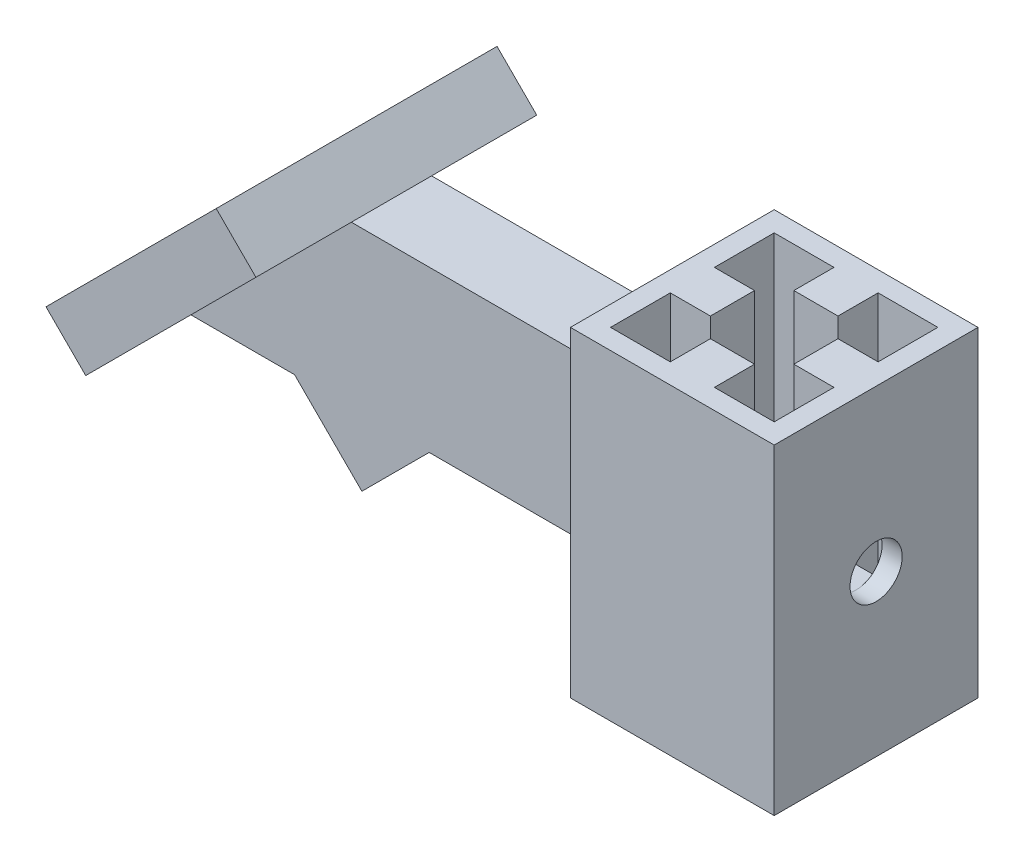
SolidWorks part; units mm, degrees
ref_plane "Alzado" through (0, 0, 0) normal (0, 0, 1) x (1, 0, 0)
ref_plane "Planta" through (0, 0, 0) normal (0, 1, 0) x (1, 0, 0)
ref_plane "Vista lateral" through (0, 0, 0) normal (1, 0, 0) x (0, 0, -1)
sketch "Croquis1" plane through (0, 0, 0) normal (0, 1, 0) x (1, 0, 0)
  line L0 (-12.7, 12.7) -> (12.7, 12.7)
  line L1 (-10.2, 10.2) -> (-2.75, 10.2)
  line L2 (-10.2, 10.2) -> (-10.2, 2.75)
  line L3 (-10.2, -10.2) -> (-2.75, -10.2)
  line L4 (10.2, 10.2) -> (10.2, 2.75)
  line L5 (-10.2, 10.2) -> (10.2, -10.2) construction
  line L6 (-10.2, -10.2) -> (10.2, 10.2) construction
  line L7 (12.7, 12.7) -> (12.7, -12.7)
  line L8 (-12.7, -12.7) -> (12.7, -12.7)
  line L9 (-12.7, 12.7) -> (-12.7, -12.7)
  line L10 (0, 12.7) -> (0, -12.7) construction
  line L11 (-12.7, 0) -> (12.7, 0) construction
  line L12 (-2.75, 10.2) -> (-2.75, 5.2)
  line L13 (-2.75, 5.2) -> (2.75, 5.2)
  line L14 (-10.2, 2.75) -> (-5.2, 2.75)
  line L15 (-5.2, 2.75) -> (-5.2, -2.75)
  line L16 (2.75, 10.2) -> (2.75, 5.2)
  line L17 (-10.2, -2.75) -> (-5.2, -2.75)
  line L18 (2.75, -10.2) -> (2.75, -5.2)
  line L19 (-2.75, -5.2) -> (2.75, -5.2)
  line L20 (-2.75, -10.2) -> (-2.75, -5.2)
  line L21 (10.2, -2.75) -> (5.2, -2.75)
  line L22 (5.2, 2.75) -> (5.2, -2.75)
  line L23 (10.2, 2.75) -> (5.2, 2.75)
  line L24 (2.75, 10.2) -> (10.2, 10.2)
  line L25 (-10.2, 10.2) -> (10.2, 10.2) construction
  line L26 (10.2, -2.75) -> (10.2, -10.2)
  line L27 (10.2, 10.2) -> (10.2, -10.2) construction
  line L28 (2.75, -10.2) -> (10.2, -10.2)
  line L29 (-10.2, -10.2) -> (10.2, -10.2) construction
  line L30 (-10.2, -2.75) -> (-10.2, -10.2)
  line L31 (-10.2, 10.2) -> (-10.2, -10.2) construction
  point P0 (0, 0)
  point P22 (0, 5.2)
  point P23 (-5.2, 0)
  dimension "D1" = 20.4
  dimension "D2" = 20.4
  dimension "D4" = 5
  dimension "D5" = 5.5
  dimension "D3" = 2.5
extrude "Saliente-Extruir1" add sketch "Croquis1" along normal blind 40
sketch "Croquis4" plane through (0, 0, 0) normal (0, 0, 1) x (1, 0, 0)
  line L5 (-12.7, 20) -> (-102.7, 20) construction
  line L11 (-70.7815, 11.8683) -> (-49.5683, 33.0815) construction
  line L14 (-52.0431, 35.5563) -> (-47.0934, 30.6066)
  line L16 (-73.2563, 14.3431) -> (-68.3066, 9.3934)
  line L17 (-73.2563, 14.3431) -> (-52.0431, 35.5563)
  line L18 (-68.3066, 9.3934) -> (-47.0934, 30.6066)
  line L19 (-12.7, 40) -> (-12.7, 0) construction
  line L20 (0, 40) -> (0, 59.061) construction
  line L21 (-12.7, 40) -> (12.7, 40) construction
  line L22 (0, 59.061) -> (0, -12.7567) construction
  point P13 (-70.7815, 11.8683)
  point P16 (-70.7815, 11.8683)
  point P17 (-49.5683, 33.0815)
  point P22 (-57.7, 20)
  dimension "D1" = 45
  dimension "D2" = 30
  dimension "D3" = 7
  dimension "D4" = 45
extrude "Saliente-Extruir3" add sketch "Croquis4" along normal mid plane 35 separate body
sketch "Croquis6" plane through (-12.7, 0, 0) normal (-1, 0, 0) x (0, 0, 1)
  line L0 (0, 40) -> (0, 0) construction
  line L1 (-12.7, 40) -> (12.7, 40) construction
  line L3 (-5, 30) -> (5, 30)
  line L4 (-5, 30) -> (-5, 10)
  line L5 (-5, 10) -> (5, 10)
  line L6 (5, 30) -> (5, 10)
  line L7 (-5, 30) -> (5, 10) construction
  line L8 (-5, 10) -> (5, 30) construction
  point P5 (0, 20)
  dimension "D1" = 20
  dimension "D2" = 10
extrude "Saliente-Extruir4" add sketch "Croquis6" along normal up to next
sketch "Croquis9" plane through (12.7, 0, 0) normal (1, 0, 0) x (0, 0, -1)
  line L0 (12.7, 20) -> (-12.7, 20) construction
  line L1 (12.7, 40) -> (12.7, 0) construction
  line L2 (-12.7, 40) -> (-12.7, 0) construction
  circle A0 centre (0, 20) radius 3.25
  dimension "D1" = 6.5
extrude "Cortar-Extruir3" cut sketch "Croquis9" against normal blind 10
sketch "Croquis10" plane through (12.7, 0, 0) normal (1, 0, 0) x (0, 0, -1)
  line L1 (-3.25, 23.25) -> (3.25, 23.25)
  line L2 (-3.25, 23.25) -> (-3.25, 16.75)
  line L3 (-3.25, 16.75) -> (3.25, 16.75)
  line L4 (3.25, 23.25) -> (3.25, 16.75)
  line L5 (-3.25, 23.25) -> (3.25, 16.75) construction
  line L6 (-3.25, 16.75) -> (3.25, 23.25) construction
  point P0 (0, 20)
  dimension "D1" = 6.5
  dimension "D2" = 6.5
extrude "Cortar-Extruir4" cut sketch "Croquis10" against normal blind 10 from surface starting at face at (10.2, 20, -5.3167)
sketch "Croquis7" plane through (-38.85, 38.85, 0) normal (0.7071, -0.7071, 0) x (0, 0, -1)
  line L0 (-17.5, -26.6579) -> (17.5, -26.6579) construction
  line L1 (-17.5, -41.6579) -> (-17.5, -11.6579) construction
  line L2 (17.5, -41.6579) -> (17.5, -11.6579) construction
  circle A0 centre (0, -26.6579) radius 3.25
  dimension "D1" = 6.5
extrude "Cortar-Extruir1" cut sketch "Croquis7" against normal through all both and the other way through all
sketch "Croquis11" plane through (-38.85, 38.85, 0) normal (0.7071, -0.7071, 0) x (0, 0, -1)
  line L0 (5, -40.8001) -> (5, -1.9092) construction
  line L1 (-5, -21.6579) -> (5, -21.6579)
  line L2 (-5, -21.6579) -> (-5, -31.6579)
  line L3 (-5, -31.6579) -> (5, -31.6579)
  line L4 (5, -21.6579) -> (5, -31.6579)
  line L5 (-5, -21.6579) -> (5, -31.6579) construction
  line L6 (-5, -31.6579) -> (5, -21.6579) construction
  circle A1 centre (0, -26.6579) radius 3.25
  point P0 (0, -26.6579)
  dimension "D1" = 10
extrude "Saliente-Extruir5" add sketch "Croquis11" along normal blind 21
sketch "Croquis12" plane through (0, 0, 5) normal (0, 0, 1) x (1, 0, 0)
  line L1 (-40.6289, 10) -> (-12.7, 10) construction
  line L2 (-38.0015, 10) -> (-40.6289, 10)
  line L3 (-40.6289, 10) -> (-39.3152, 8.6863)
  line L4 (-39.3152, 8.6863) -> (-38.0015, 10)
extrude "Saliente-Extruir6" add sketch "Croquis12" against normal up to vertex (10 mm away) up to point (-40.6289, 10, -5)
